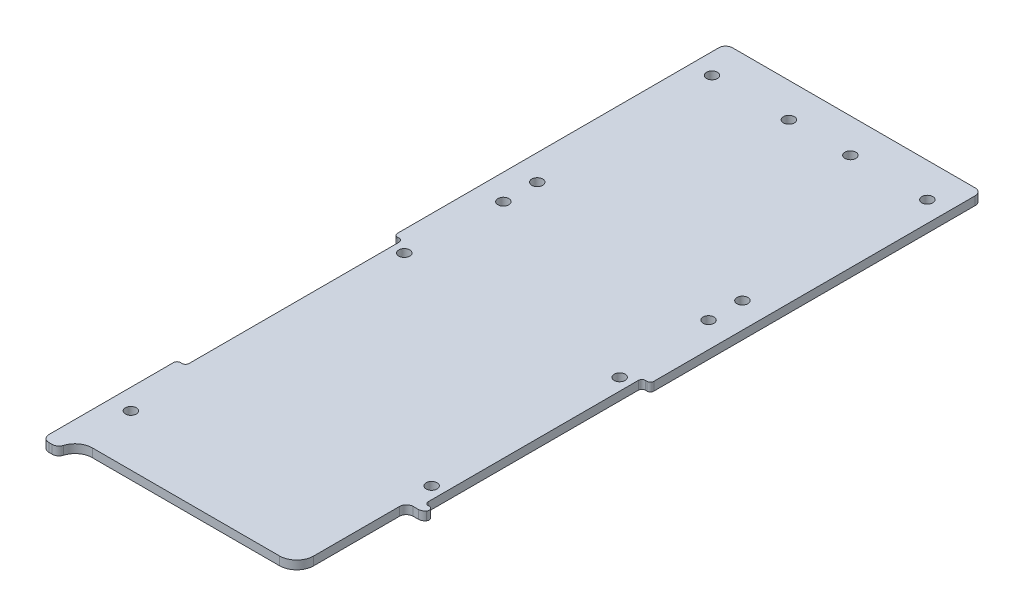
SolidWorks part; units mm, degrees
ref_plane "Front Plane" through (0, 0, 0) normal (0, 0, 1) x (1, 0, 0)
ref_plane "Top Plane" through (0, 0, 0) normal (0, 1, 0) x (1, 0, 0)
ref_plane "Right Plane" through (0, 0, 0) normal (1, 0, 0) x (0, 0, -1)
sketch "Sketch1" plane through (0, 0, 0) normal (0, 1, 0) x (1, 0, 0)
  line L0 (-39.9997, 0) -> (-39.9997, 114.3) construction
  line L1 (-47.625, 127) -> (47.625, 127)
  line L2 (-47.625, 127) -> (-47.625, -127)
  line L3 (-47.625, -127) -> (47.625, -127)
  line L4 (47.625, 127) -> (47.625, -127)
  line L5 (-47.625, 127) -> (47.625, -127) construction
  line L6 (-47.625, -127) -> (47.625, 127) construction
  line L7 (0, 0) -> (0, 127) construction
  line L8 (-39.9997, 0) -> (-39.9997, -101.6) construction
  line L9 (-39.9997, 0) -> (0, 0) construction
  line L10 (-41.275, -127) -> (-41.275, -120.65)
  line L11 (-41.275, -120.65) -> (41.275, -120.65)
  line L12 (41.275, -120.65) -> (41.275, -127)
  line L13 (-39.9997, 114.3) -> (-11.4247, 114.3) construction
  line L14 (39.9997, 114.3) -> (11.4247, 114.3) construction
  circle A0 centre (-39.9997, 114.3) radius 2.032
  circle A1 centre (-39.9997, 0) radius 2.032
  circle A2 centre (-39.9997, -101.6) radius 2.032
  circle A3 centre (39.9997, -101.6) radius 2.032
  circle A4 centre (39.9997, 0) radius 2.032
  circle A5 centre (39.9997, 114.3) radius 2.032
  circle A6 centre (-11.4247, 114.3) radius 2.032
  circle A7 centre (11.4247, 114.3) radius 2.032
  circle A8 centre (-39.9997, -69.85) radius 2.032
  circle A9 centre (39.9997, -69.85) radius 2.032
  point P0 (0, 0)
  dimension "D4" = 4.064
  dimension "D10" = 28.575
  dimension "D1" = 95.25
  dimension "D2" = 254
  dimension "D3" = 7.6253
  dimension "D5" = 12.7
  dimension "D6" = 25.4
  dimension "D7" = 6.35
  dimension "D8" = 6.35
  dimension "D9" = 6.35
  dimension "D11" = 69.85
extrude "Boss-Extrude1" add sketch "Sketch1" along normal blind 3.175 contours L4 L1 L2 L3 A4 A0 A1 A2 A3 A5 | A8 | A3 region at (0, 0, -2.6944) region at (39.9997, 0, 101.6) region at (-39.9997, 0, 69.85)
fillet "Fillet1" radius 2.54 4 edges at (-47.625, 1.5875, -127) (47.625, 1.5875, -127) (47.625, 1.5875, 127) (-47.625, 1.5875, 127)
fillet "Fillet2" radius 2.54 2 edges at (41.275, 1.5875, 127) (-41.275, 1.5875, 127)
fillet "Fillet3" radius 6.35 2 edges at (41.275, 1.5875, 120.65) (-41.275, 1.5875, 120.65)
sketch "Sketch2" plane through (0, 0, 0) normal (0, -1, 0) x (1, 0, 0)
  line L1 (43.815, 127) -> (45.085, 127) construction
  line L2 (40.6451, 123.5787) -> (40.6451, 79.8881)
  line L3 (40.6451, 79.8881) -> (47.625, 79.8881)
  line L11 (47.625, -124.46) -> (47.625, 124.46) construction
  line L12 (43.815, 127) -> (45.085, 127)
  line L13 (47.625, 79.8881) -> (47.625, 124.46)
  arc A0 (35.2956, 120.65) -> (41.3809, 125.1857) centre (35.2956, 127) ccw construction
  arc A1 (43.815, 127) -> (41.3809, 125.1857) centre (43.815, 124.46) ccw construction
  arc A2 (47.625, 124.46) -> (45.085, 127) centre (45.085, 124.46) ccw construction
  arc A3 (40.6451, 123.5787) -> (41.3809, 125.1857) centre (35.2956, 127) ccw
  arc A4 (43.815, 127) -> (41.3809, 125.1857) centre (43.815, 124.46) ccw
  arc A5 (47.625, 124.46) -> (45.085, 127) centre (45.085, 124.46) ccw
  dimension "D2" = 47.1119
  dimension "D1" = 6.9799
extrude "Cut-Extrude1" cut sketch "Sketch2" against normal through all
fillet "Fillet4" radius 6.35 1 edges at (40.6451, 1.5875, 123.5787)
fillet "Fillet5" radius 2.54 2 edges at (47.625, 1.5875, 79.8881) (40.6451, 1.5875, 79.8881)
sketch "Sketch3" plane through (0, 0, 0) normal (0, -1, 0) x (1, 0, 0)
  line L0 (-36.3049, -49.7791) -> (-39.9117, -49.7791) construction
  line L1 (-40.4197, -49.276) -> (-40.4197, -45.7043) construction
  line L2 (-35.7969, -45.7043) -> (-35.7969, -49.276) construction
  line L3 (-39.9117, -45.2013) -> (-36.3049, -45.2013) construction
  line L4 (-36.3049, -37.2027) -> (-39.9117, -37.2027) construction
  line L5 (-35.7969, -33.1279) -> (-35.7969, -36.6996) construction
  line L6 (-40.4197, -36.6996) -> (-40.4197, -33.1279) construction
  line L7 (-39.9117, -32.6249) -> (-36.3049, -32.6249) construction
  line L8 (36.2883, -32.6249) -> (39.8951, -32.6249) construction
  line L9 (40.4031, -33.1279) -> (40.4031, -36.6996) construction
  line L10 (39.8951, -37.2027) -> (36.2883, -37.2027) construction
  line L11 (35.7803, -36.6996) -> (35.7803, -33.1279) construction
  line L12 (36.2883, -45.2013) -> (39.8951, -45.2013) construction
  line L13 (35.7803, -49.276) -> (35.7803, -45.7043) construction
  line L14 (40.4031, -45.7043) -> (40.4031, -49.276) construction
  line L15 (39.8951, -49.7791) -> (36.2883, -49.7791) construction
  line L16 (-36.3049, -49.7791) -> (-39.9117, -49.7791)
  line L17 (-40.4197, -49.276) -> (-40.4197, -45.7043)
  line L18 (-35.7969, -45.7043) -> (-35.7969, -49.276)
  line L19 (-39.9117, -45.2013) -> (-36.3049, -45.2013)
  line L20 (-36.3049, -37.2027) -> (-39.9117, -37.2027)
  line L21 (-35.7969, -33.1279) -> (-35.7969, -36.6996)
  line L22 (-40.4197, -36.6996) -> (-40.4197, -33.1279)
  line L23 (-39.9117, -32.6249) -> (-36.3049, -32.6249)
  line L24 (36.2883, -32.6249) -> (39.8951, -32.6249)
  line L25 (40.4031, -33.1279) -> (40.4031, -36.6996)
  line L26 (39.8951, -37.2027) -> (36.2883, -37.2027)
  line L27 (35.7803, -36.6996) -> (35.7803, -33.1279)
  line L28 (36.2883, -45.2013) -> (39.8951, -45.2013)
  line L29 (35.7803, -49.276) -> (35.7803, -45.7043)
  line L30 (40.4031, -45.7043) -> (40.4031, -49.276)
  line L31 (39.8951, -49.7791) -> (36.2883, -49.7791)
  line L32 (-47.625, -25.836) -> (47.625, -25.836)
  line L33 (-47.625, -124.46) -> (-47.625, 124.46) construction
  line L34 (47.625, -124.46) -> (47.625, 77.3481) construction
  line L35 (0, -25.836) -> (0, -56.0686) construction
  line L1362 (-40.4197, -34.9138) -> (-35.7969, -34.9138)
  line L1857 (-38.1083, -32.6249) -> (-38.1083, -37.2027)
  line L1858 (-38.1083, -45.2013) -> (-38.1083, -49.7791)
  line L1859 (-40.4197, -47.4902) -> (-35.7969, -47.4902)
  circle A0 centre (-38.1083, -34.9138) radius 2.032
  circle A1 centre (-38.1083, -47.4902) radius 2.032
  circle A2 centre (38.1083, -47.4902) radius 2.032
  circle A3 centre (38.1083, -34.9138) radius 2.032
  ellipse E0 centre (-39.9117, -45.7043) end of major axis (-39.4037, -45.7043) minor radius 0.5031 (-39.9117, -45.2013) -> (-40.4197, -45.7043) ccw construction
  ellipse E1 centre (-39.9117, -49.276) end of major axis (-39.4037, -49.276) minor radius 0.5031 (-40.4197, -49.276) -> (-39.9117, -49.7791) ccw construction
  ellipse E6 centre (-36.3049, -49.276) end of major axis (-35.7969, -49.276) minor radius 0.5031 (-36.3049, -49.7791) -> (-35.7969, -49.276) ccw construction
  ellipse E7 centre (-36.3049, -45.7043) end of major axis (-35.7969, -45.7043) minor radius 0.5031 (-35.7969, -45.7043) -> (-36.3049, -45.2013) ccw construction
  ellipse E8 centre (-39.9117, -36.6996) end of major axis (-39.4037, -36.6996) minor radius 0.5031 (-40.4197, -36.6996) -> (-39.9117, -37.2027) ccw construction
  ellipse E9 centre (-36.3049, -36.6996) end of major axis (-35.7969, -36.6996) minor radius 0.5031 (-36.3049, -37.2027) -> (-35.7969, -36.6996) ccw construction
  ellipse E10 centre (-36.3049, -33.1279) end of major axis (-35.7969, -33.1279) minor radius 0.5031 (-35.7969, -33.1279) -> (-36.3049, -32.6249) ccw construction
  ellipse E11 centre (-39.9117, -33.1279) end of major axis (-39.4037, -33.1279) minor radius 0.5031 (-39.9117, -32.6249) -> (-40.4197, -33.1279) ccw construction
  ellipse E12 centre (39.8951, -33.1279) end of major axis (40.4031, -33.1279) minor radius 0.5031 (40.4031, -33.1279) -> (39.8951, -32.6249) ccw construction
  ellipse E13 centre (36.2883, -33.1279) end of major axis (36.7963, -33.1279) minor radius 0.5031 (36.2883, -32.6249) -> (35.7803, -33.1279) ccw construction
  ellipse E14 centre (39.8951, -36.6996) end of major axis (40.4031, -36.6996) minor radius 0.5031 (39.8951, -37.2027) -> (40.4031, -36.6996) ccw construction
  ellipse E15 centre (36.2883, -36.6996) end of major axis (36.7963, -36.6996) minor radius 0.5031 (35.7803, -36.6996) -> (36.2883, -37.2027) ccw construction
  ellipse E16 centre (36.2883, -45.7043) end of major axis (36.7963, -45.7043) minor radius 0.5031 (36.2883, -45.2013) -> (35.7803, -45.7043) ccw construction
  ellipse E17 centre (36.2883, -49.276) end of major axis (36.7963, -49.276) minor radius 0.5031 (35.7803, -49.276) -> (36.2883, -49.7791) ccw construction
  ellipse E18 centre (39.8951, -45.7043) end of major axis (40.4031, -45.7043) minor radius 0.5031 (40.4031, -45.7043) -> (39.8951, -45.2013) ccw construction
  ellipse E19 centre (39.8951, -49.276) end of major axis (40.4031, -49.276) minor radius 0.5031 (39.8951, -49.7791) -> (40.4031, -49.276) ccw construction
  ellipse E20 centre (-39.9117, -45.7043) end of major axis (-39.4037, -45.7043) minor radius 0.5031 (-39.9117, -45.2013) -> (-40.4197, -45.7043) ccw
  ellipse E21 centre (-39.9117, -49.276) end of major axis (-39.4037, -49.276) minor radius 0.5031 (-40.4197, -49.276) -> (-39.9117, -49.7791) ccw
  ellipse E22 centre (-36.3049, -49.276) end of major axis (-35.7969, -49.276) minor radius 0.5031 (-36.3049, -49.7791) -> (-35.7969, -49.276) ccw
  ellipse E23 centre (-36.3049, -45.7043) end of major axis (-35.7969, -45.7043) minor radius 0.5031 (-35.7969, -45.7043) -> (-36.3049, -45.2013) ccw
  ellipse E24 centre (-39.9117, -36.6996) end of major axis (-39.4037, -36.6996) minor radius 0.5031 (-40.4197, -36.6996) -> (-39.9117, -37.2027) ccw
  ellipse E25 centre (-36.3049, -36.6996) end of major axis (-35.7969, -36.6996) minor radius 0.5031 (-36.3049, -37.2027) -> (-35.7969, -36.6996) ccw
  ellipse E26 centre (-36.3049, -33.1279) end of major axis (-35.7969, -33.1279) minor radius 0.5031 (-35.7969, -33.1279) -> (-36.3049, -32.6249) ccw
  ellipse E27 centre (-39.9117, -33.1279) end of major axis (-39.4037, -33.1279) minor radius 0.5031 (-39.9117, -32.6249) -> (-40.4197, -33.1279) ccw
  ellipse E28 centre (39.8951, -33.1279) end of major axis (40.4031, -33.1279) minor radius 0.5031 (40.4031, -33.1279) -> (39.8951, -32.6249) ccw
  ellipse E29 centre (36.2883, -33.1279) end of major axis (36.7963, -33.1279) minor radius 0.5031 (36.2883, -32.6249) -> (35.7803, -33.1279) ccw
  ellipse E30 centre (39.8951, -36.6996) end of major axis (40.4031, -36.6996) minor radius 0.5031 (39.8951, -37.2027) -> (40.4031, -36.6996) ccw
  ellipse E31 centre (36.2883, -36.6996) end of major axis (36.7963, -36.6996) minor radius 0.5031 (35.7803, -36.6996) -> (36.2883, -37.2027) ccw
  ellipse E32 centre (36.2883, -45.7043) end of major axis (36.7963, -45.7043) minor radius 0.5031 (36.2883, -45.2013) -> (35.7803, -45.7043) ccw
  ellipse E33 centre (36.2883, -49.276) end of major axis (36.7963, -49.276) minor radius 0.5031 (35.7803, -49.276) -> (36.2883, -49.7791) ccw
  ellipse E34 centre (39.8951, -45.7043) end of major axis (40.4031, -45.7043) minor radius 0.5031 (40.4031, -45.7043) -> (39.8951, -45.2013) ccw
  ellipse E35 centre (39.8951, -49.276) end of major axis (40.4031, -49.276) minor radius 0.5031 (39.8951, -49.7791) -> (40.4031, -49.276) ccw
  dimension "D2" = 4.064
extrude "Cut-Extrude2" cut sketch "Sketch3" against normal through all contours A0 | A1 | A2 | A3
sketch "Sketch4" plane through (0, 3.175, 0) normal (0, 1, 0) x (1, 0, 0)
  line L11 (-47.625, 124.46) -> (-47.625, -124.46) construction
  line L12 (-47.625, -76.835) -> (-44.45, -76.835)
  line L13 (-47.625, -76.835) -> (-47.625, 3.81)
  line L15 (-47.625, 3.81) -> (-44.45, 3.81)
  line L16 (-44.45, -76.835) -> (-44.45, 3.81)
  line L17 (47.625, 124.46) -> (47.625, -77.3481) construction
  line L18 (47.625, -76.835) -> (44.45, -76.835)
  line L19 (47.625, -76.835) -> (47.625, 3.81)
  line L20 (47.625, 3.81) -> (44.45, 3.81)
  line L45 (44.45, -76.835) -> (44.45, 3.81)
  line L47 (43.1851, -79.8881) -> (45.085, -79.8881) construction
  dimension "D1" = 3.175
  dimension "D2" = 80.645
  dimension "D3" = 3.0531
extrude "Cut-Extrude3" cut sketch "Sketch4" against normal through all and the other way through all
fillet "Fillet6" radius 1.27 8 edges at (-44.45, 1.5875, -3.81) (-47.625, 1.5875, -3.81) (-47.625, 1.5875, 76.835) (-44.45, 1.5875, 76.835) (44.45, 1.5875, 76.835) (47.625, 1.5875, 76.835) (44.45, 1.5875, -3.81) (47.625, 1.5875, -3.81)
